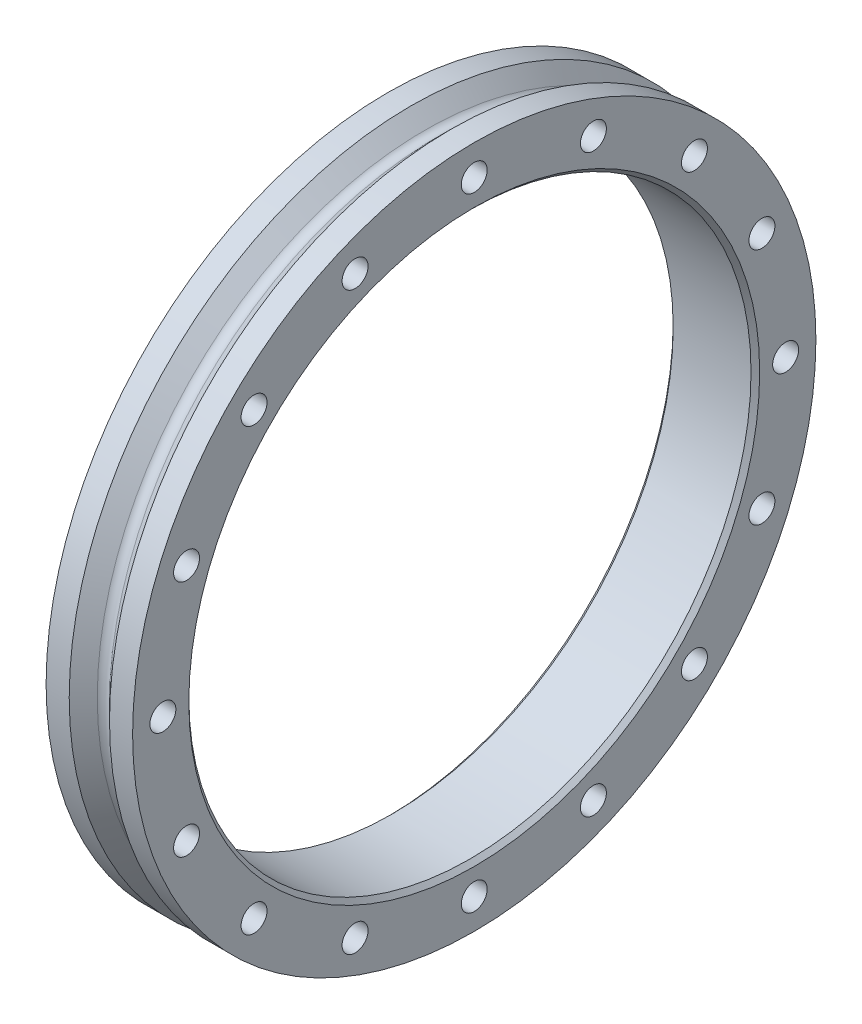
SolidWorks part; units mm, degrees
ref_plane "Front Plane" through (0, 0, 0) normal (0, 0, 1) x (1, 0, 0)
ref_plane "Top Plane" through (0, 0, 0) normal (0, 1, 0) x (1, 0, 0)
ref_plane "Right Plane" through (0, 0, 0) normal (1, 0, 0) x (0, 0, -1)
sketch "Sketch1" plane through (0, 0, 0) normal (0, 0, 1) x (1, 0, 0)
  line L0 (-42.0673, 0) -> (0, 0) construction
  line L1 (0, 0) -> (0, 88) construction
  line L2 (0, 85.6569) -> (5.6569, 80)
  line L3 (10, 95) -> (-10, 95)
  line L4 (10, 95) -> (10, 81)
  line L5 (10, 81) -> (-10, 81)
  line L6 (-10, 95) -> (-10, 81)
  line L7 (10, 95) -> (-10, 81) construction
  line L8 (10, 81) -> (-10, 95) construction
  line L9 (10, 79) -> (-10, 79)
  line L10 (10, 79) -> (10, 65)
  line L11 (10, 65) -> (-10, 65)
  line L12 (-10, 79) -> (-10, 65)
  line L13 (10, 79) -> (-10, 65) construction
  line L14 (10, 65) -> (-10, 79) construction
  line L15 (0, 85.6569) -> (-5.6569, 80)
  line L16 (5.6569, 80) -> (0, 74.3431)
  line L17 (-5.6569, 80) -> (0, 74.3431)
  line L18 (0, 85.6569) -> (0, 74.3431) construction
  line L19 (5.6569, 80) -> (-5.6569, 80) construction
  point P8 (0, 72)
  point P14 (0, 80)
  dimension "D1" = 20
  dimension "D2" = 65
  dimension "D3" = 95
  dimension "D4" = 14
  dimension "D5" = 1
  dimension "D6" = 8
revolve "Revolve1" add sketch "Sketch1" angle 360 about L0 region at (0, 71.5426, 0)
ref_axis "Axis1" through (10, 0, 0) along (-1, 0, 0)
chamfer "Chamfer1" distance 1 angle 45 2 edges at (10, 0, 65) (-10, 0, 65)
fillet "Fillet1" radius 2 1 edges at (0, 0, 74.3431)
sketch "Sketch2" plane through (10, 0, 0) normal (1, 0, 0) x (0, 0, -1)
  circle A0 centre (0, 72) radius 3
  dimension "D1" = 72
  dimension "D2" = 6
extrude "Cut-Extrude1" cut sketch "Sketch2" against normal through all
pattern_circular "CirPattern1" count 16 over 360 about axis through (10, 0, 0) along (-1, 0, 0) of "Cut-Extrude1"
